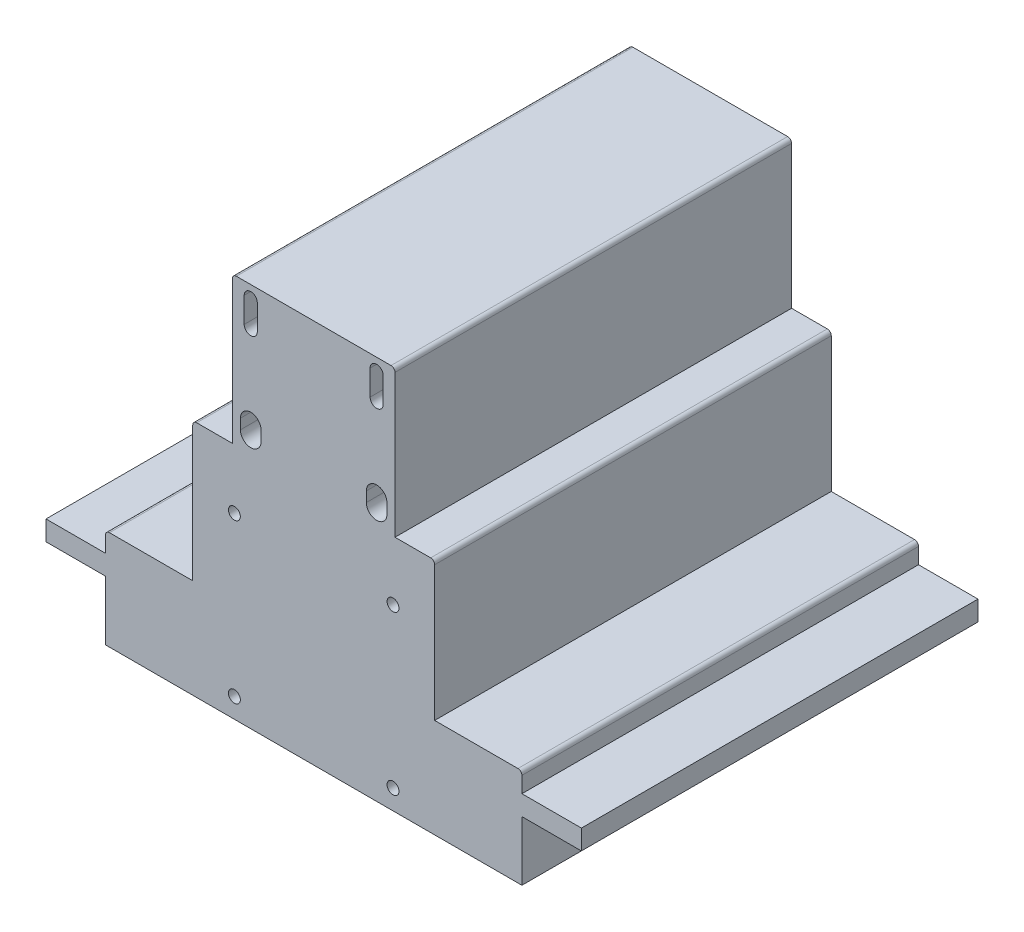
SolidWorks part; units mm, degrees
ref_plane "Front Plane" through (0, 0, 0) normal (0, 0, 1) x (1, 0, 0)
ref_plane "Top Plane" through (0, 0, 0) normal (0, 1, 0) x (1, 0, 0)
ref_plane "Right Plane" through (0, 0, 0) normal (1, 0, 0) x (0, 0, -1)
sketch "Sketch1" plane through (0, 0, 0) normal (0, 0, 1) x (1, 0, 0)
  line L0 (0, 0) -> (10.5, 0)
  line L1 (10.5, 0) -> (10.5, 1.5)
  line L2 (10.5, 1.5) -> (12, 1.5)
  line L3 (12, 1.5) -> (12, 2)
  line L4 (12, 2) -> (10.5, 2)
  line L5 (10.5, 2) -> (10.5, 2.5)
  line L6 (10.5, 2.5) -> (8.3, 2.5)
  line L7 (8.3, 2.5) -> (8.3, 6)
  line L8 (8.3, 6) -> (7.3, 6)
  line L9 (7.3, 6) -> (7.3, 9.7)
  line L10 (7.3, 9.7) -> (3.2, 9.7)
  line L11 (3.2, 9.7) -> (3.2, 6)
  line L12 (3.2, 6) -> (2.2, 6)
  line L13 (2.2, 6) -> (2.2, 2.5)
  line L14 (2.2, 2.5) -> (0, 2.5)
  line L15 (0, 2.5) -> (0, 2)
  line L16 (0, 2) -> (-1.5, 2)
  line L17 (-1.5, 2) -> (-1.5, 1.5)
  line L18 (-1.5, 1.5) -> (0, 1.5)
  line L19 (0, 1.5) -> (0, 0)
  line L20 (3.6625, 9.382) -> (3.6625, 8.747) construction
  line L21 (3.8275, 9.382) -> (3.8275, 8.747)
  line L22 (3.4975, 9.382) -> (3.4975, 8.747)
  line L23 (5.25, 8.3596) -> (5.25, 0.9482) construction
  line L24 (6.8375, 9.382) -> (6.8375, 8.747) construction
  line L25 (6.6725, 9.382) -> (6.6725, 8.747)
  line L26 (7.0025, 9.382) -> (7.0025, 8.747)
  line L27 (3.6625, 6.3975) -> (3.6625, 6.6515) construction
  line L28 (3.4025, 6.3975) -> (3.4025, 6.6515)
  line L29 (3.9225, 6.3975) -> (3.9225, 6.6515)
  line L30 (6.8375, 6.3975) -> (6.8375, 6.6515) construction
  line L31 (7.0975, 6.3975) -> (7.0975, 6.6515)
  line L32 (6.5775, 6.3975) -> (6.5775, 6.6515)
  arc A0 (3.8275, 9.382) -> (3.4975, 9.382) centre (3.6625, 9.382) ccw
  arc A1 (3.4975, 8.747) -> (3.8275, 8.747) centre (3.6625, 8.747) ccw
  circle A2 centre (3.25, 0.5) radius 0.15
  circle A3 centre (7.25, 0.5) radius 0.15
  circle A4 centre (7.25, 4.5) radius 0.15
  circle A5 centre (3.25, 4.5) radius 0.15
  arc A6 (6.6725, 9.382) -> (7.0025, 9.382) centre (6.8375, 9.382) cw
  arc A7 (7.0025, 8.747) -> (6.6725, 8.747) centre (6.8375, 8.747) cw
  arc A8 (3.4025, 6.3975) -> (3.9225, 6.3975) centre (3.6625, 6.3975) ccw
  arc A9 (3.9225, 6.6515) -> (3.4025, 6.6515) centre (3.6625, 6.6515) ccw
  arc A10 (7.0975, 6.3975) -> (6.5775, 6.3975) centre (6.8375, 6.3975) cw
  arc A11 (6.5775, 6.6515) -> (7.0975, 6.6515) centre (6.8375, 6.6515) cw
  point P11 (3.6625, 9.0645)
  point P36 (3.6625, 6.5245)
  point P42 (6.8375, 9.0645)
  point P54 (6.8375, 6.5245)
  dimension "D11" = 0.3
  dimension "D14" = 4
  dimension "D15" = 0.5
  dimension "D16" = 4
  dimension "D17" = 4
  dimension "D20" = 0.165
  dimension "D22" = 0.26
  dimension "D1" = 10.5
  dimension "D2" = 1.5
  dimension "D3" = 1.5
  dimension "D4" = 0.5
  dimension "D5" = 0.5
  dimension "D6" = 2.2
  dimension "D7" = 3.5
  dimension "D8" = 1
  dimension "D9" = 3.7
  dimension "D10" = 0.635
  dimension "D12" = 4
  dimension "D13" = 4
  dimension "D18" = 3.175
  dimension "D19" = 0.318
  dimension "D21" = 2.54
  dimension "D23" = 0.254
extrude "Boss-Extrude1" add sketch "Sketch1" along normal blind 10
fillet "Fillet2" radius 0.1 6 edges at (0, 2.5, 5) (2.2, 6, 5) (10.5, 2.5, 5) (8.3, 6, 5) (7.3, 9.7, 5) (3.2, 9.7, 5)
